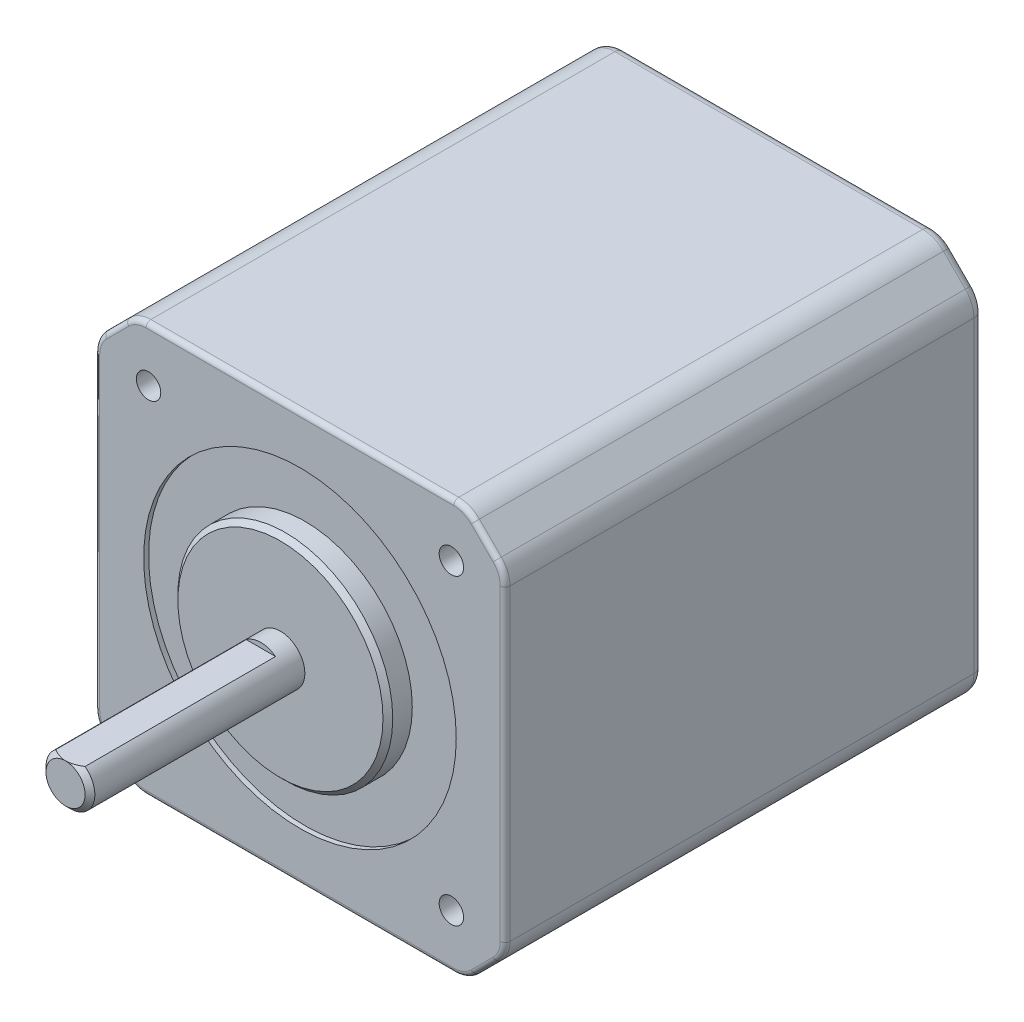
SolidWorks part; units mm, degrees
material "Commercially Pure CP-Ti UNS R50400 (SS)"
ref_plane "Front Plane" through (0, 0, 0) normal (0, 0, 1) x (1, 0, 0)
ref_plane "Top Plane" through (0, 0, 0) normal (0, 1, 0) x (1, 0, 0)
ref_plane "Right Plane" through (0, 0, 0) normal (1, 0, 0) x (0, 0, -1)
sketch "Sketch1" plane through (0, 0, 0) normal (0, 0, 1) x (1, 0, 0)
  line L1 (-21, -21) -> (21, -21)
  line L2 (-21, -21) -> (-21, 21)
  line L3 (-21, 21) -> (21, 21)
  line L4 (21, -21) -> (21, 21)
  line L5 (-21, -21) -> (21, 21) construction
  line L6 (-21, 21) -> (21, -21) construction
  point P0 (0, 0)
  dimension "D1" = 42
  dimension "D2" = 42
extrude "Boss-Extrude1" add sketch "Sketch1" along normal mid plane 49
chamfer "Chamfer1" distance 4 angle 45 4 edges at (-21, -21, 0) (21, -21, 0) (-21, 21, 0) (21, 21, 0)
sketch "Sketch2" plane through (0, 0, 24.5) normal (0, 0, 1) x (1, 0, 0)
  circle A0 centre (0, 0) radius 11
  dimension "D1" = 22
extrude "Boss-Extrude2" add sketch "Sketch2" along normal blind 2
sketch "Sketch3" plane through (0, 0, 24.5) normal (0, 0, 1) x (1, 0, 0)
  circle A0 centre (0, 0) radius 16
  circle A1 centre (0, 0) radius 11
  dimension "D1" = 32
extrude "Cut-Extrude1" cut sketch "Sketch3" against normal blind 0.5
sketch "Sketch4" plane through (0, 0, 26.5) normal (0, 0, 1) x (1, 0, 0)
  circle A0 centre (0, 0) radius 2.5
  dimension "D1" = 5
extrude "Boss-Extrude3" add sketch "Sketch4" along normal blind 22
sketch "Sketch5" plane through (0, 0, 48.5) normal (0, 0, 1) x (1, 0, 0)
  line L1 (-4.4436, 2) -> (5.9206, 2)
  line L2 (-4.4436, 2) -> (-4.4436, 3.526)
  line L3 (-4.4436, 3.526) -> (5.9206, 3.526)
  line L4 (5.9206, 2) -> (5.9206, 3.526)
  dimension "D1" = 2
extrude "Cut-Extrude2" cut sketch "Sketch5" against normal blind 20
hole_wizard "M3x0.5 Tapped Hole1" positions "Sketch6" profile "Sketch7" tap size "M3x0.5" standard "ANSI Metric"
sketch "Sketch6" plane through (0, 0, 24.5) normal (0, 0, 1) x (1, 0, 0)
  point P0 (-15.5, 15.5)
  dimension "D1" = 15.5
  dimension "D2" = 15.5
sketch "Sketch7" plane through (-15.5, 15.5, 24.5) normal (1, 0, 0) x (0, -1, 0)
  line L0 (0, 0) -> (0, 8.2511)
  line L1 (0, 8.2511) -> (1.25, 7.5)
  line L2 (1.25, 7.5) -> (1.25, 0)
  line L5 (1.25, 0) -> (0, 0)
  line L10 (0, 8.2511) -> (-1.25, 7.5) construction
  line L11 (0, -6.35) -> (0, 107.95) construction
  dimension "Tap Drill Dia." = 2.5
  dimension "Tap Drill Depth" = 7.5
  dimension "Drill Angle" = 118
cosmetic thread "Hole Thread1" parameters "D1"=6, "D2"=3
pattern_circular "CirPattern1" count 4 over 360 about axis through (0, 0, 26.5) along (0, 0, -1) of "M3x0.5 Tapped Hole1"
fillet "Fillet1" radius 3 8 edges at (-21, -17, 0) (-17, -21, 0) (17, -21, 0) (21, -17, 0) (21, 17, 0) (17, 21, 0) (-21, 17, 0) (-17, 21, 0)
chamfer "Chamfer2" distance 0.5 angle 45 2 edges at (0, -2.5, 48.5) (11, 0, 26.5)
fillet "Fillet2" radius 1 16 edges at (16.9054, 20.7716, -24.5) (19, 19, -24.5) (20.7716, 16.9054, -24.5) (21, 0, -24.5) (20.7716, -16.9054, -24.5) (19, -19, -24.5) (16.9054, -20.7716, -24.5) (0, -21, -24.5) (-16.9054, -20.7716, -24.5) (-19, -19, -24.5) (-20.7716, -16.9054, -24.5) (-21, 0, -24.5) (-20.7716, 16.9054, -24.5) (-19, 19, -24.5) (-16.9054, 20.7716, -24.5) (0, 21, -24.5)
fillet "Fillet3" radius 0.5 16 edges at (16.9054, 20.7716, 24.5) (19, 19, 24.5) (20.7716, 16.9054, 24.5) (21, 0, 24.5) (20.7716, -16.9054, 24.5) (19, -19, 24.5) (16.9054, -20.7716, 24.5) (0, -21, 24.5) (-16.9054, -20.7716, 24.5) (-19, -19, 24.5) (-20.7716, -16.9054, 24.5) (-21, 0, 24.5) (-20.7716, 16.9054, 24.5) (-19, 19, 24.5) (-16.9054, 20.7716, 24.5) (0, 21, 24.5)
sketch "Sketch8" plane through (0, -21, 0) normal (0, -1, 0) x (1, 0, 0)
  circle A1 centre (0, -18.5744) radius 0.65
  circle A2 centre (1.1585, -19.5) radius 0.65
  circle A3 centre (0.0324, -20.3521) radius 0.65
  circle A4 centre (-1.1368, -19.5) radius 0.65
  dimension "D3" = 1.3
  dimension "D4" = 1.3
  dimension "D5" = 1.3
  dimension "D6" = 1.3
extrude "Boss-Extrude4" add sketch "Sketch8" along normal blind 2
sketch "Sketch9" plane through (0, 0, -24.5) normal (0, 0, -1) x (-1, 0, 0)
  circle A0 centre (0, 0) radius 3.5
  dimension "D1" = 7
extrude "Cut-Extrude3" cut sketch "Sketch9" against normal blind 3.5
sketch "Sketch10" plane through (0, 0, -21) normal (0, 0, -1) x (-1, 0, 0)
  circle A0 centre (0, 0) radius 2.5
  dimension "D1" = 5
extrude "Boss-Extrude5" add sketch "Sketch10" along normal blind 18.5
sketch "Sketch11" plane through (0, 0, -39.5) normal (0, 0, -1) x (-1, 0, 0)
  line L0 (-2.4749, 1.9656) -> (2.8441, 2.0399)
  line L1 (2.8441, 2.0399) -> (0.2301, 6.6065)
  line L2 (0.2301, 6.6065) -> (-2.4749, 1.9656)
  circle A0 centre (0, 0) radius 3.5 construction
  dimension "D1" = 2
extrude "Cut-Extrude4" cut sketch "Sketch11" against normal blind 14
chamfer "Chamfer3" distance 0.5 angle 45 1 edges at (-0.0349, -2.4998, -39.5)
